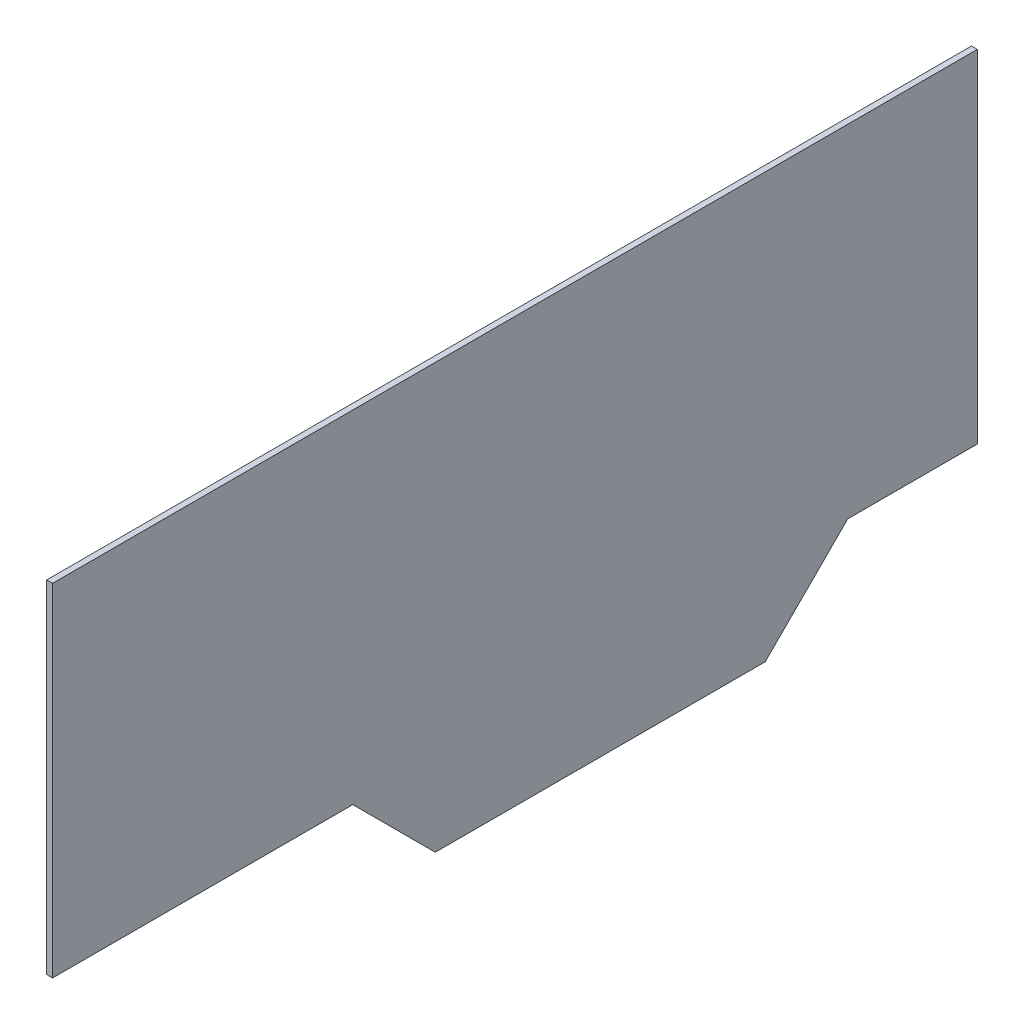
SolidWorks part; units mm, degrees
material "6061-T6 (SS)"
ref_plane "X-Y Datum" through (0, 0, 0) normal (0, 0, 1) x (1, 0, 0)
ref_plane "X-Z Datum" through (0, 0, 0) normal (0, 1, 0) x (1, 0, 0)
ref_plane "Y-Z Datum" through (0, 0, 0) normal (1, 0, 0) x (0, 0, -1)
sketch "Sketch1" plane through (0, 0, 0) normal (1, 0, 0) x (0, 0, -1)
  line L1 (-249.174, 88.9) -> (249.174, 88.9)
  line L2 (-249.174, 88.9) -> (-249.174, -88.9)
  line L3 (-249.174, -88.9) -> (249.174, -88.9)
  line L4 (249.174, 88.9) -> (249.174, -88.9)
  line L5 (-249.174, 88.9) -> (249.174, -88.9) construction
  line L6 (-249.174, -88.9) -> (249.174, 88.9) construction
  point P0 (0, 0)
  dimension "D1" = 177.8
  dimension "D2" = 498.348
extrude "Boss-Extrude1" add sketch "Sketch1" along normal mid plane 3.175
sketch "Sketch2" plane through (1.5875, 0, 0) normal (1, 0, 0) x (0, 0, -1)
  line L0 (249.174, -88.9) -> (249.174, -95.25)
  line L1 (249.174, -95.25) -> (179.324, -95.25)
  line L2 (179.324, -95.25) -> (134.874, -139.7)
  line L3 (134.874, -139.7) -> (-42.926, -139.7)
  line L5 (-249.174, -88.9) -> (249.174, -88.9) construction
  line L6 (-249.174, -88.9) -> (249.174, -88.9)
  line L7 (-42.926, -139.7) -> (-87.376, -95.25)
  line L8 (-87.376, -95.25) -> (-249.174, -95.25)
  line L9 (-249.174, -95.25) -> (-249.174, -88.9)
  line L10 (249.174, -88.9) -> (249.174, 88.9) construction
  line L11 (-249.174, 88.9) -> (-249.174, -88.9) construction
  line M10 (-249.174, -88.9) -> (249.174, -88.9)
  dimension "D1" = 6.35
  dimension "D2" = 69.85
  dimension "D3" = 50.8
  dimension "D4" = 177.8
  dimension "D5" = 6.35
  dimension "D6" = 135
  dimension "D7" = 135
extrude "Boss-Extrude2" add sketch "Sketch2" against normal blind 3.175 contours L3 L2 L1 L0 M10 region at (1.5875, -110.1905, -34.8202)
